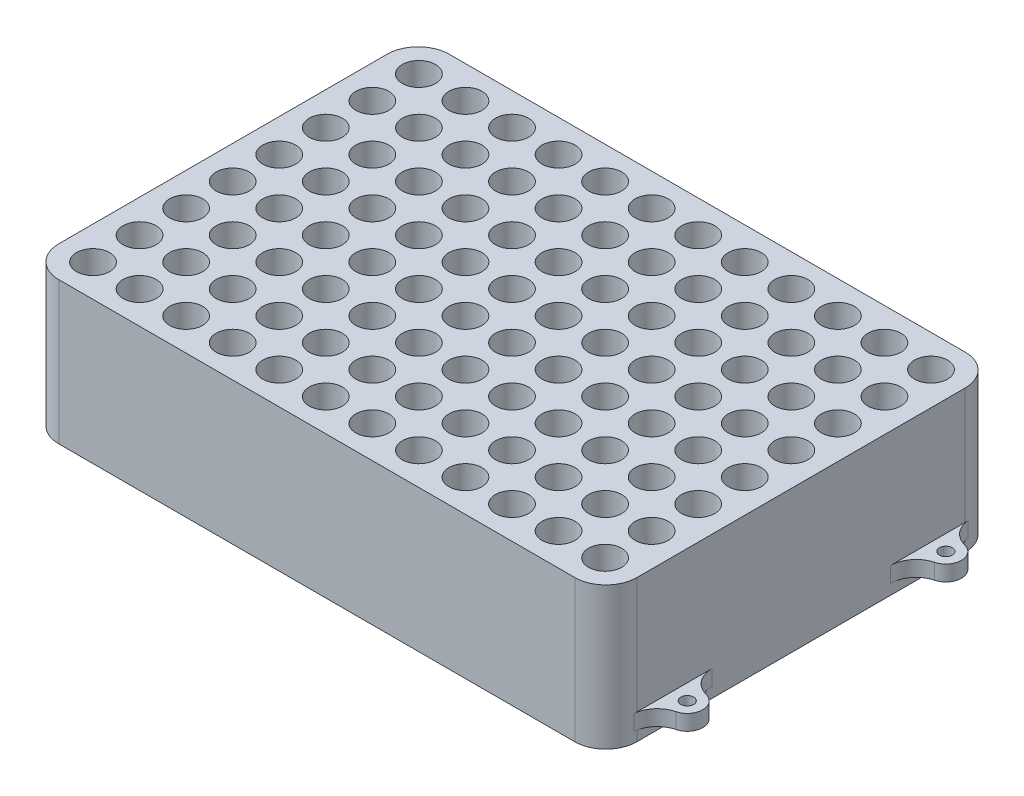
SolidWorks part; units mm, degrees
material "Alliage 6061"
ref_plane "Plan de face" through (0, 0, 0) normal (0, 0, 1) x (1, 0, 0)
ref_plane "Plan de dessus" through (0, 0, 0) normal (0, 1, 0) x (1, 0, 0)
ref_plane "Plan de droite" through (0, 0, 0) normal (1, 0, 0) x (0, 0, -1)
sketch "Esquisse1" plane through (0, 0, 0) normal (0, 1, 0) x (1, 0, 0)
  line L0 (-55.88, 40.74) -> (55.88, 40.74)
  line L1 (-61.88, 34.74) -> (-61.88, -34.74)
  line L2 (-55.88, -40.74) -> (55.88, -40.74)
  line L3 (61.88, 34.74) -> (61.88, -34.74)
  line L4 (-61.88, 40.74) -> (61.88, -40.74) construction
  line L5 (-61.88, -40.74) -> (61.88, 40.74) construction
  line L6 (0, -12.2243) -> (0, 12.7445) construction
  line L7 (-15.0853, 0) -> (18.4665, 0) construction
  arc A0 (-61.88, -34.74) -> (-55.88, -40.74) centre (-55.88, -34.74) ccw
  arc A1 (55.88, -40.74) -> (61.88, -34.74) centre (55.88, -34.74) ccw
  arc A2 (55.88, 40.74) -> (61.88, 34.74) centre (55.88, 34.74) cw
  arc A3 (-55.88, 40.74) -> (-61.88, 34.74) centre (-55.88, 34.74) ccw
  point P0 (0, 0)
  dimension "D3" = 6
  dimension "D1" = 81.48
  dimension "D2" = 123.76
extrude "Base Stock" add sketch "Esquisse1" along normal blind 27.5
sketch "Esquisse2" plane through (0, 27.5, 0) normal (0, 1, 0) x (1, 0, 0)
  circle A0 centre (-49.5, 31.5) radius 3.2
  circle A1 centre (-40.5, 31.5) radius 3.2
  circle A2 centre (-31.5, 31.5) radius 3.2
  circle A3 centre (-22.5, 31.5) radius 3.2
  circle A4 centre (-13.5, 31.5) radius 3.2
  circle A5 centre (-4.5, 31.5) radius 3.2
  circle A6 centre (4.5, 31.5) radius 3.2
  circle A7 centre (13.5, 31.5) radius 3.2
  circle A8 centre (22.5, 31.5) radius 3.2
  circle A9 centre (31.5, 31.5) radius 3.2
  circle A10 centre (40.5, 31.5) radius 3.2
  circle A11 centre (49.5, 31.5) radius 3.2
  circle A12 centre (-40.5, 22.5) radius 3.2
  circle A13 centre (-31.5, 22.5) radius 3.2
  circle A14 centre (-22.5, 22.5) radius 3.2
  circle A15 centre (-13.5, 22.5) radius 3.2
  circle A16 centre (-4.5, 22.5) radius 3.2
  circle A17 centre (4.5, 22.5) radius 3.2
  circle A18 centre (13.5, 22.5) radius 3.2
  circle A19 centre (22.5, 22.5) radius 3.2
  circle A20 centre (31.5, 22.5) radius 3.2
  circle A21 centre (40.5, 22.5) radius 3.2
  circle A22 centre (49.5, 22.5) radius 3.2
  circle A23 centre (-40.5, 13.5) radius 3.2
  circle A24 centre (-31.5, 13.5) radius 3.2
  circle A25 centre (-22.5, 13.5) radius 3.2
  circle A26 centre (-13.5, 13.5) radius 3.2
  circle A27 centre (-4.5, 13.5) radius 3.2
  circle A28 centre (4.5, 13.5) radius 3.2
  circle A29 centre (13.5, 13.5) radius 3.2
  circle A30 centre (22.5, 13.5) radius 3.2
  circle A31 centre (31.5, 13.5) radius 3.2
  circle A32 centre (40.5, 13.5) radius 3.2
  circle A33 centre (49.5, 13.5) radius 3.2
  circle A34 centre (-40.5, 4.5) radius 3.2
  circle A35 centre (-31.5, 4.5) radius 3.2
  circle A36 centre (-22.5, 4.5) radius 3.2
  circle A37 centre (-13.5, 4.5) radius 3.2
  circle A38 centre (-4.5, 4.5) radius 3.2
  circle A39 centre (4.5, 4.5) radius 3.2
  circle A40 centre (13.5, 4.5) radius 3.2
  circle A41 centre (22.5, 4.5) radius 3.2
  circle A42 centre (31.5, 4.5) radius 3.2
  circle A43 centre (40.5, 4.5) radius 3.2
  circle A44 centre (49.5, 4.5) radius 3.2
  circle A45 centre (-40.5, -4.5) radius 3.2
  circle A46 centre (-31.5, -4.5) radius 3.2
  circle A47 centre (-22.5, -4.5) radius 3.2
  circle A48 centre (-13.5, -4.5) radius 3.2
  circle A49 centre (-4.5, -4.5) radius 3.2
  circle A50 centre (4.5, -4.5) radius 3.2
  circle A51 centre (13.5, -4.5) radius 3.2
  circle A52 centre (22.5, -4.5) radius 3.2
  circle A53 centre (31.5, -4.5) radius 3.2
  circle A54 centre (40.5, -4.5) radius 3.2
  circle A55 centre (49.5, -4.5) radius 3.2
  circle A56 centre (-40.5, -13.5) radius 3.2
  circle A57 centre (-31.5, -13.5) radius 3.2
  circle A58 centre (-22.5, -13.5) radius 3.2
  circle A59 centre (-13.5, -13.5) radius 3.2
  circle A60 centre (-4.5, -13.5) radius 3.2
  circle A61 centre (4.5, -13.5) radius 3.2
  circle A62 centre (13.5, -13.5) radius 3.2
  circle A63 centre (22.5, -13.5) radius 3.2
  circle A64 centre (31.5, -13.5) radius 3.2
  circle A65 centre (40.5, -13.5) radius 3.2
  circle A66 centre (49.5, -13.5) radius 3.2
  circle A67 centre (-40.5, -22.5) radius 3.2
  circle A68 centre (-31.5, -22.5) radius 3.2
  circle A69 centre (-22.5, -22.5) radius 3.2
  circle A70 centre (-13.5, -22.5) radius 3.2
  circle A71 centre (-4.5, -22.5) radius 3.2
  circle A72 centre (4.5, -22.5) radius 3.2
  circle A73 centre (13.5, -22.5) radius 3.2
  circle A74 centre (22.5, -22.5) radius 3.2
  circle A75 centre (31.5, -22.5) radius 3.2
  circle A76 centre (40.5, -22.5) radius 3.2
  circle A77 centre (49.5, -22.5) radius 3.2
  circle A78 centre (-40.5, -31.5) radius 3.2
  circle A79 centre (-31.5, -31.5) radius 3.2
  circle A80 centre (-22.5, -31.5) radius 3.2
  circle A81 centre (-13.5, -31.5) radius 3.2
  circle A82 centre (-4.5, -31.5) radius 3.2
  circle A83 centre (4.5, -31.5) radius 3.2
  circle A84 centre (13.5, -31.5) radius 3.2
  circle A85 centre (22.5, -31.5) radius 3.2
  circle A86 centre (31.5, -31.5) radius 3.2
  circle A87 centre (40.5, -31.5) radius 3.2
  circle A88 centre (49.5, -31.5) radius 3.2
  circle A89 centre (-49.5, 22.5) radius 3.2
  circle A90 centre (-49.5, 13.5) radius 3.2
  circle A91 centre (-49.5, 4.5) radius 3.2
  circle A92 centre (-49.5, -4.5) radius 3.2
  circle A93 centre (-49.5, -13.5) radius 3.2
  circle A94 centre (-49.5, -22.5) radius 3.2
  circle A95 centre (-49.5, -31.5) radius 3.2
  dimension "D1" = 6.4
  dimension "D2" = 49.5
  dimension "D3" = 31.5
  dimension "D4" = 12
  dimension "D5" = 8
extrude "Vials holes" cut sketch "Esquisse2" against normal through all
sketch "Esquisse3" plane through (0, 27.5, 0) normal (0, 1, 0) x (1, 0, 0)
  line L0 (-49.88, 37.74) -> (49.88, 37.74)
  line L1 (-55.88, 31.74) -> (-55.88, -31.74)
  line L2 (-49.88, -37.74) -> (49.88, -37.74)
  line L3 (55.88, 31.74) -> (55.88, -31.74)
  line L4 (-55.88, 37.74) -> (55.88, -37.74) construction
  line L5 (-55.88, -37.74) -> (55.88, 37.74) construction
  line L7 (-80.6812, 49.6479) -> (71.5461, 49.6479)
  line L8 (-80.6812, 49.6479) -> (-80.6812, -47.9405)
  line L9 (-80.6812, -47.9405) -> (71.5461, -47.9405)
  line L10 (71.5461, 49.6479) -> (71.5461, -47.9405)
  arc A0 (-55.88, -31.74) -> (-49.88, -37.74) centre (-49.88, -31.74) ccw
  arc A1 (49.88, -37.74) -> (55.88, -31.74) centre (49.88, -31.74) ccw
  arc A2 (49.88, 37.74) -> (55.88, 31.74) centre (49.88, 31.74) cw
  arc A3 (-49.88, 37.74) -> (-55.88, 31.74) centre (-49.88, 31.74) ccw
  point P0 (0, 0)
  dimension "D3" = 6
  dimension "D1" = 111.76
  dimension "D2" = 75.48
extrude "Enlèv. mat.-Extru.2" cut sketch "Esquisse3" against normal through all
sketch "Esquisse4" plane through (0, 0, 0) normal (0, -1, 0) x (1, 0, 0)
  line L0 (49.45, -34.9) -> (-49.45, -34.9)
  line L1 (52.9, -31.45) -> (52.9, 31.45)
  line L2 (49.45, 34.9) -> (-49.45, 34.9)
  line L3 (-52.9, -31.45) -> (-52.9, 31.45)
  line L4 (52.9, -34.9) -> (-52.9, 34.9) construction
  line L5 (52.9, 34.9) -> (-52.9, -34.9) construction
  line L6 (52.7, -34.7) -> (46.3, -34.7) construction
  line L7 (52.7, -34.7) -> (52.7, -28.3) construction
  line L8 (52.7, -28.3) -> (46.3, -28.3) construction
  line L9 (46.3, -34.7) -> (46.3, -28.3) construction
  line L10 (52.7, -34.7) -> (46.3, -28.3) construction
  line L11 (52.7, -28.3) -> (46.3, -34.7) construction
  arc A0 (52.9, 31.45) -> (49.45, 34.9) centre (49.45, 31.45) ccw
  arc A1 (-49.45, 34.9) -> (-52.9, 31.45) centre (-49.45, 31.45) ccw
  arc A2 (-49.45, -34.9) -> (-52.9, -31.45) centre (-49.45, -31.45) cw
  arc A3 (49.45, -34.9) -> (52.9, -31.45) centre (49.45, -31.45) ccw
  point P0 (0, 0)
  point P5 (49.5, -31.5)
  dimension "D3" = 3.45
  dimension "D1" = 0.2
  dimension "D2" = 0.2
extrude "Enlèv. mat.-Extru.3" cut sketch "Esquisse4" against normal blind 20
sketch "Esquisse5" plane through (0, 0, 0) normal (0, 1, 0) x (1, 0, 0)
  line L0 (0, 40.3156) -> (0, -40.3156) construction
  line L1 (-55.88, 0) -> (55.88, 0) construction
  line L2 (58.88, -28) -> (55.88, -28)
  line L3 (58.88, -22) -> (55.88, -22)
  line L4 (55.88, -28) -> (55.88, -22)
  line L5 (-58.88, -28) -> (-55.88, -28)
  line L6 (-58.88, -22) -> (-55.88, -22)
  line L7 (-55.88, -28) -> (-55.88, -22)
  line L8 (-58.88, 22) -> (-55.88, 22)
  line L9 (-55.88, 28) -> (-55.88, 22)
  line L10 (-58.88, 28) -> (-55.88, 28)
  line L11 (58.88, 28) -> (55.88, 28)
  line L12 (58.88, 22) -> (55.88, 22)
  line L13 (55.88, 28) -> (55.88, 22)
  line L14 (55.88, -31.74) -> (55.88, 31.74) construction
  line L16 (-5.2435, 0) -> (4.8024, 0) construction
  line L17 (-20.075, 0) -> (20.075, 0) construction
  arc A0 (58.88, -28) -> (58.88, -22) centre (58.88, -25) ccw
  arc A1 (-58.88, -28) -> (-58.88, -22) centre (-58.88, -25) cw
  arc A2 (-58.88, 28) -> (-58.88, 22) centre (-58.88, 25) ccw
  arc A3 (58.88, 28) -> (58.88, 22) centre (58.88, 25) cw
  point P24 (0, 0)
  dimension "D1" = 6
  dimension "D2" = 25
extrude "Boss.-Extru.2" add sketch "Esquisse5" along normal blind 3 from offset 2
fillet "Congé1" radius 5 8 edges at (55.88, 3.5, -22) (55.88, 3.5, 28) (-55.88, 3.5, 28) (-55.88, 3.5, -22) (-55.88, 3.5, 22) (-55.88, 3.5, -28) (55.88, 3.5, 22) (55.88, 3.5, -28)
sketch "Esquisse8" plane through (0, 5, 0) normal (0, 1, 0) x (1, 0, 0)
  line L0 (0, -15.125) -> (0, 15.125) construction
  point P0 (-58.88, 25)
  point P3 (-58.88, -25)
  point P8 (58.88, 25)
  point P9 (58.88, -25)
hole_wizard "Trou taraudé M31" positions "Esquisse8" profile "Esquisse7" tap size "M3" standard "ISO" end condition through all
sketch "Esquisse7" plane through (-58.88, 5, -25) normal (1, 0, 0) x (0, 0, 1)
  line L0 (0, 0) -> (0, 5)
  line L1 (0, 5) -> (1.25, 5)
  line L2 (1.25, 5) -> (1.25, 0)
  line L5 (1.25, 0) -> (0, 0)
  line L11 (0, -6.35) -> (0, 107.95) construction
  dimension "Diamètre du trou pour taraudage jusqu'au prochain" = 2.5
  dimension "Profondeur du trou pour taraudage jusqu'au prochain" = 5
cosmetic thread "Filetage de perçage1" parameters "D2"=3
cosmetic thread "Filetage de perçage2" parameters "D2"=3
cosmetic thread "Filetage de perçage3" parameters "D2"=3
cosmetic thread "Filetage de perçage4" parameters "D2"=3
sketch "Esquisse10" plane through (0, 5, 0) normal (0, 1, 0) x (1, 0, 0)
  line L0 (0, -15.125) -> (0, 15.125) construction
  line L1 (-15.125, 0) -> (15.125, 0) construction
  circle A0 centre (-58.88, 25) radius 1.4
  circle A1 centre (58.88, 25) radius 1.4
  circle A2 centre (58.88, -25) radius 1.4
  circle A3 centre (-58.88, -25) radius 1.4
  dimension "D1" = 2.8
extrude "Version 3d printed" [suppressed] cut sketch "Esquisse10" against normal through all
equation "\"Hauteur\"= 27.5"
